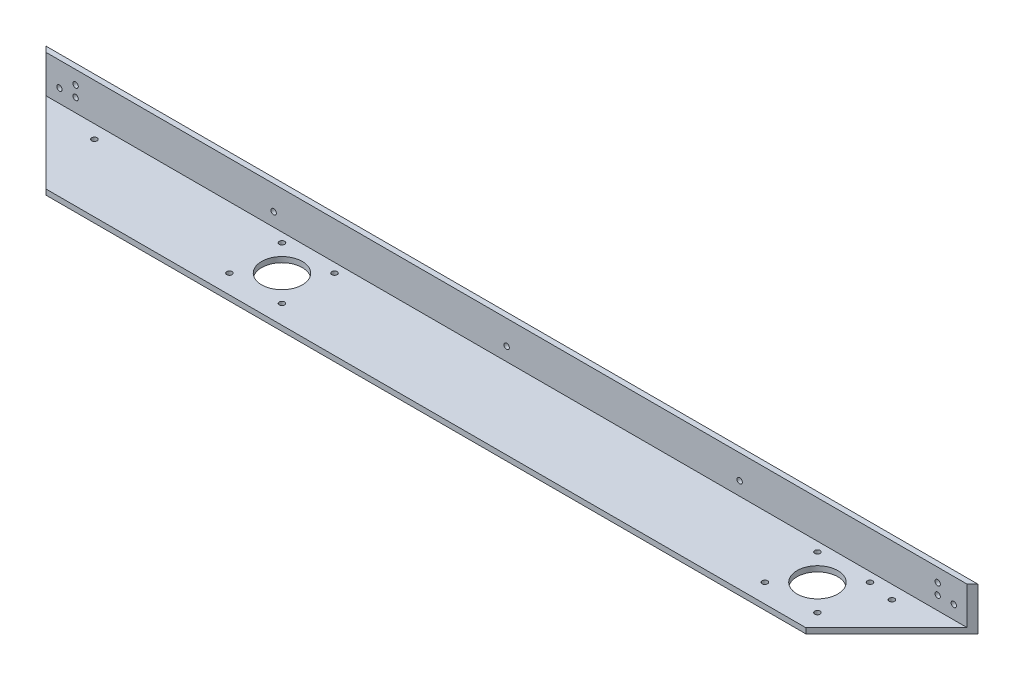
SolidWorks part; units mm, degrees
ref_plane "Front Plane" through (0, 0, 0) normal (0, 0, 1) x (1, 0, 0)
ref_plane "Top Plane" through (0, 0, 0) normal (0, 1, 0) x (1, 0, 0)
ref_plane "Right Plane" through (0, 0, 0) normal (1, 0, 0) x (0, 0, -1)
sketch "Sketch1" plane through (0, 0, 0) normal (1, 0, 0) x (0, 0, -1)
  line L0 (0, 0) -> (-50.8, 0)
  line L1 (-50.8, 0) -> (-50.8, 3.175)
  line L2 (-50.8, 3.175) -> (-3.175, 3.175)
  line L3 (-3.175, 3.175) -> (-3.175, 25.4)
  line L4 (-3.175, 25.4) -> (0, 25.4)
  line L5 (0, 25.4) -> (0, 0)
  dimension "LHeight" = 25.4
  dimension "LWidth" = 50.8
  dimension "LMaterialThickness" = 3.175
  dimension "D1" = 47.625
  dimension "D2" = 22.225
  dimension "D3" = 3.175
extrude "Boss-Extrude1" add sketch "Sketch1" along normal blind 550
chamfer "Chamfer7" distance 50.8 angle 45 1 edges at (0, 1.5875, 50.8)
chamfer "Chamfer8" distance 50.8 angle 45 1 edges at (550, 1.5875, 50.8)
sketch "BotthomHoles-Sketch2" plane through (0, 3.175, 0) normal (0, 1, 0) x (1, 0, 0)
  line L0 (546.825, -3.175) -> (3.175, -3.175) construction
  line L1 (550, 0) -> (0, 0) construction
  circle A0 centre (479.425, -24.175) radius 12
  circle A2 centre (463.925, -8.675) radius 1.5875
  circle A3 centre (494.925, -8.675) radius 1.5875
  circle A6 centre (463.925, -39.675) radius 1.5875
  circle A7 centre (494.925, -39.675) radius 1.5875
  circle A8 centre (39.6875, -11.1125) radius 1.5875
  circle A9 centre (510.3125, -11.1125) radius 1.5875
  circle A10 centre (178.925, -39.675) radius 1.5875
  circle A11 centre (147.925, -39.675) radius 1.5875
  circle A12 centre (178.925, -8.675) radius 1.5875
  circle A13 centre (147.925, -8.675) radius 1.5875
  circle A14 centre (163.425, -24.175) radius 12
  dimension "D9" = 3.175
  dimension "D10" = 24
  dimension "D13" = 3.175
  dimension "D2" = 8.675
  dimension "D5" = 15.5
  dimension "D6" = 31
  dimension "D7" = 15.5
  dimension "D8" = 31
  dimension "D11" = 21
  dimension "D3" = 70.575
  dimension "D4" = 11.1125
  dimension "D12" = 39.6875
  dimension "D14" = 39.6875
  dimension "D15" = 31
  dimension "D16" = 15.5
  dimension "D17" = 316
extrude "BottomHoles-Cut-Extrude1" cut sketch "BotthomHoles-Sketch2" against normal through all
sketch "RightSideHoles-Sketch3" plane through (0, 0, 0) normal (0, 0, -1) x (-1, 0, 0)
  line L0 (-550, 0) -> (-550, 25.4) construction
  line L1 (0, 0) -> (0, 25.4) construction
  line L2 (-550, 25.4) -> (0, 25.4) construction
  circle A1 centre (-529.3625, 17.4625) radius 1.5875
  circle A2 centre (-538.8875, 11.1125) radius 1.5875
  circle A3 centre (-529.3625, 11.1125) radius 1.5875
  circle A4 centre (-11.1125, 11.1125) radius 1.5875
  circle A5 centre (-20.6375, 11.1125) radius 1.5875
  circle A6 centre (-20.6375, 17.4625) radius 1.5875
  circle A8 centre (-412.5, 11.1125) radius 1.5875
  circle A9 centre (-275, 11.1125) radius 1.5875
  circle A10 centre (-137.5, 11.1125) radius 1.5875
  dimension "D4" = 11.1125
  dimension "D7" = 3.175
  dimension "D2" = 20.6375
  dimension "D6" = 20.6375
  dimension "D8" = 137.5
  dimension "D9" = 137.5
  dimension "D10" = 137.5
  dimension "D5" = 11.1125
  dimension "D11" = 11.1125
  dimension "D3" = 7.9375
extrude "RightSideHoles-Cut-Extrude2" cut sketch "RightSideHoles-Sketch3" against normal through all
equation "\"LowerRailWidth\"= 2.00in"
equation "\"LowerRailHeight\"= 1.00in"
equation "\"RailThickness\"= .125in'Spec"
equation "\"SideRailHoleY1FromEdge\"= \"HoleOffsetFromEdge\""
equation "\"SideRailHoleX1FromSide\"= \"HoleOffsetFromSide\""
equation "\"StepperHoleDiameter\"= 24mm"
equation "\"StepperMountingHoleDiameter\"= 3.175mm"
equation "\"SideRailLength\"= 550mm"
equation "\"StepperMountingHoleDistance\"= 31mm'Spec"
equation "\"VSWidth\"= 1.25in'Spec"
equation "\"StepperMountingHoleOffsetFromLeftOrRightSide\"= \"StepperMountingHoleOffsetFromItsSide\" + \"RailThickness\""
equation "\"HoleOffsetFromEdge\"= \"RailThickness\" * 2.5"
equation "\"HoleOffsetFromSide\"= \"RailThickness\" * 3.5"
equation "\"StepperMountingHoleOffsetFromItsSide\"= 5.5mm'Spec"
equation "\"SideRailHoleX2FromSide\"= \"VSWidth\" - \"HoleOffsetFromEdge\" - \"RailThickness\"'Equals 20.6375"
equation "\"FasteningHoleDiameter\"= .125in"
equation "\"SideRailHoleY2FromSide\"= \"HoleOffsetFromSide\""
equation "\"LHeight@Sketch1\"=\"LowerRailHeight\""
equation "\"LWidth@Sketch1\"=\"LowerRailWidth\""
equation "\"D1@Chamfer7\"=\"LowerRailWidth\""
equation "\"D1@Chamfer8\"=\"LowerRailWidth\""
equation "\"D2@BotthomHoles-Sketch2\" = \"StepperMountingHoleOffsetFromLeftOrRightSide\""
equation "\"D5@BotthomHoles-Sketch2\" = \"StepperMountingHoleDistance\" / 2"
equation "\"D6@BotthomHoles-Sketch2\" = \"StepperMountingHoleDistance\""
equation "\"D7@BotthomHoles-Sketch2\" = \"StepperMountingHoleDistance\" / 2"
equation "\"D8@BotthomHoles-Sketch2\" = \"StepperMountingHoleDistance\""
equation "\"D9@BotthomHoles-Sketch2\" = \"StepperMountingHoleDiameter\""
equation "\"D10@BotthomHoles-Sketch2\" = \"StepperHoleDiameter\""
equation "\"D2@RightSideHoles-Sketch3\" = \"SideRailHoleX2FromSide\""
equation "\"D4@RightSideHoles-Sketch3\" = \"SideRailHoleY2FromSide\""
equation "\"D7@RightSideHoles-Sketch3\" = \"FasteningHoleDiameter\""
equation "\"D1@Boss-Extrude1\"=\"SideRailLength\""
equation "\"D6@RightSideHoles-Sketch3\"=\"SideRailHoleX2FromSide\""
equation "\"BedOverlap\"= 20mm"
equation "\"BedThirdSize\"= 70mm"
equation "\"BedInnerSquareWidth\"= \"BedThirdSize\" * 3'Equals 210"
equation "\"BedInnerSquareLength\"= \"BedInnerSquareWidth\""
equation "\"BedLWidth\"= \"BedThirdSize\" + \"BedOverlap\"'Equals 90"
equation "\"BedLength\"= \"BedInnerSquareLength\" + \"BedLWidth\" * 2 - \"BedOverlap\" * 2 + \"BedIncreasedByLength\"'Equals 350"
equation "\"DistanceBetweenFrontToBackStepperHoles\"= \"BedLength\" - \"DistanceFromBedFrontToFirstLeftStepperHole\"'Equals 316"
equation "\"D3@BotthomHoles-Sketch2\"=\"DistanceFromFrontSideToFirstLeftStepperHole\""
equation "\"DistanceFromBedFrontToFirstLeftStepperHole\"= \"LeadScrewNutPadSize\" + 10mm'Equals 34"
equation "\"DistanceFromFrontSideToBedFront\"= \"RailThickness\" + \"BeltTensionerDepth\" + 10mm'Equals 36.575"
equation "\"20TGT2PulleyDiameter\"= 17.9mm'Spec"
equation "\"BeltTensionerBackWallThickness\"= 4mm"
equation "\"BeltTensionerSpaceBetweenPulleyAndWall\"= 1.5mm"
equation "\"BeltTensionerInnerDepth\"= \"20TGT2PulleyDiameter\" + \"BeltTensionerSpaceBetweenPulleyAndWall\""
equation "\"BeltTensionerDepth\"= \"BeltTensionerBackWallThickness\" + \"BeltTensionerInnerDepth\"'Equals 23.4"
equation "\"BedIncreasedByLength\"= 0mm"
equation "\"LowerCornerBlockWidth\"= \"LowerRailWidth\" - \"RailThickness\" * 2'Room for left front stepper"
equation "\"D4@BotthomHoles-Sketch2\"=\"LowerCornerBlockY1FromSide\""
equation "\"D12@BotthomHoles-Sketch2\"=\"LowerCornerBlockX1FromSide\""
equation "\"D13@BotthomHoles-Sketch2\"=\"FasteningHoleDiameter\""
equation "\"D14@BotthomHoles-Sketch2\"=\"LowerCornerBlockX1FromSide\""
equation "\"LowerCornerBlockX1FromSide\"= \"LowerCornerBlockWidth\" - \"HoleOffsetFromEdge\" + \"RailThickness\""
equation "\"LowerCornerBlockY1FromSide\"= \"HoleOffsetFromSide\""
equation "\"D15@BotthomHoles-Sketch2\"=\"StepperMountingHoleDistance\""
equation "\"D16@BotthomHoles-Sketch2\"=\"StepperMountingHoleDistance\"/2"
equation "\"D17@BotthomHoles-Sketch2\"=\"DistanceBetweenFrontToBackStepperHoles\""
equation "\"DistanceFromFrontSideToFirstLeftStepperHole\"= \"DistanceFromFrontSideToBedFront\" + \"DistanceFromBedFrontToFirstLeftStepperHole\"'Equals 70.575"
equation "\"LeadScrewNutMountingHoleFlangeDiameter\"= 22mm'Spec"
equation "\"LeadScrewNutPadSize\"= \"LeadScrewNutMountingHoleFlangeDiameter\" + 2mm'Equals 24"
equation "\"LeftOrRightEnclosureOffsets\"= \"SideRailLength\" / 4"
equation "\"D8@RightSideHoles-Sketch3\"=\"LeftOrRightEnclosureOffsets\""
equation "\"D9@RightSideHoles-Sketch3\"=\"LeftOrRightEnclosureOffsets\""
equation "\"D10@RightSideHoles-Sketch3\"=\"LeftOrRightEnclosureOffsets\""
equation "\"D5@RightSideHoles-Sketch3\"=\"SideRailHoleX1FromSide\""
equation "\"D11@RightSideHoles-Sketch3\"=\"SideRailHoleX1FromSide\""
equation "\"D3@RightSideHoles-Sketch3\"=\"SideRailHoleY1FromEdge\""
